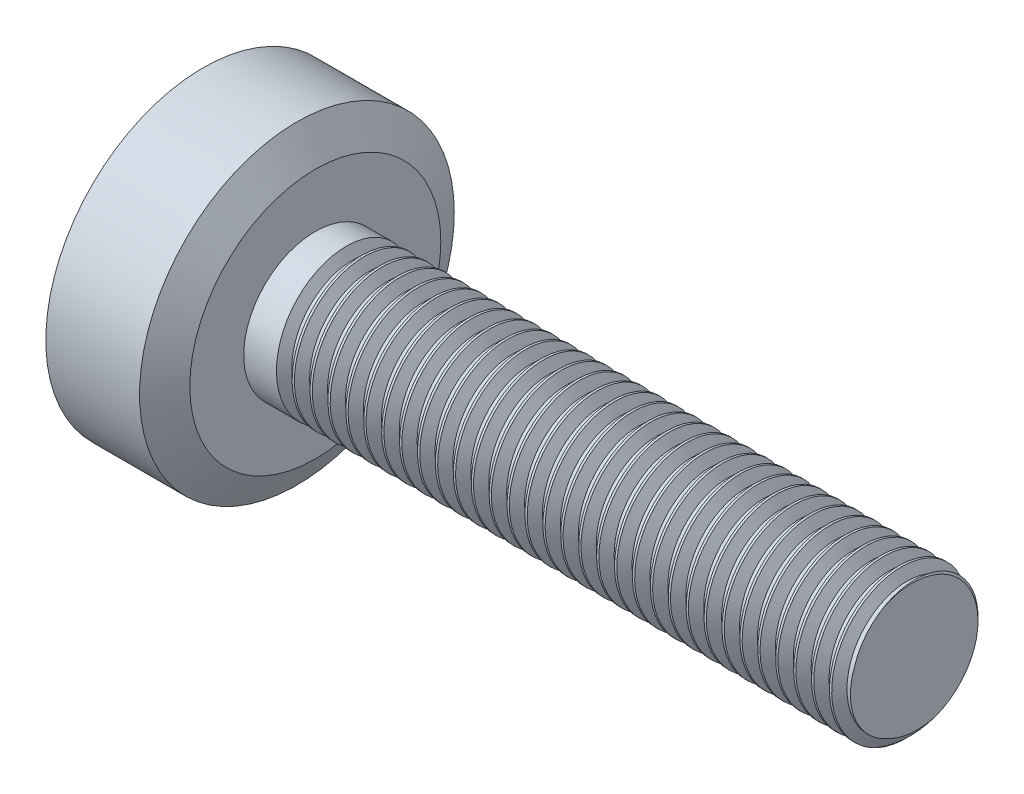
SolidWorks part; units mm, degrees
ref_plane "Front Plane" through (0, 0, 0) normal (0, 0, 1) x (1, 0, 0)
ref_plane "Top Plane" through (0, 0, 0) normal (0, 1, 0) x (1, 0, 0)
ref_plane "Right Plane" through (0, 0, 0) normal (1, 0, 0) x (0, 0, -1)
sketch "Sketch3" plane through (0, 0, 0) normal (0, 1, 0) x (1, 0, 0)
  line L0 (0, 0) -> (62, 0) construction
  line L1 (0, 0) -> (0, 9)
  line L2 (0, 9) -> (2.6092, 13.1776)
  line L3 (2.6092, 13.1776) -> (10.46, 13.1776)
  line L4 (10.46, 13.1776) -> (12, 10.5103)
  line L5 (12, 10.5103) -> (12, 6)
  line L6 (12, 6) -> (62, 6)
  line L7 (62, 6) -> (62, 0)
  line L8 (62, 0) -> (0, 0)
  dimension "D1" = 6
  dimension "D2" = 50
  dimension "D3" = 12
  dimension "D4" = 9
revolve "Revolve1" add sketch "Sketch3" angle 360 about L8
chamfer "Chamfer1" distance 0.5 angle 45 1 edges at (62, 0, -6)
sketch "Sketch4" plane through (0, 0, 0) normal (-1, 0, 0) x (0, 0, 1)
  line L1 (4.5, -2.5981) -> (4.5, 2.5981)
  line L2 (4.5, 2.5981) -> (0, 5.1962)
  line L3 (0, 5.1962) -> (-4.5, 2.5981)
  line L4 (-4.5, 2.5981) -> (-4.5, -2.5981)
  line L5 (-4.5, -2.5981) -> (0, -5.1962)
  line L6 (0, -5.1962) -> (4.5, -2.5981)
  circle A0 centre (0, 0) radius 4.5 construction
  dimension "D1" = 9
extrude "Cut-Extrude1" cut sketch "Sketch4" against normal blind 8
sketch "Sketch5" plane through (0, 0, 0) normal (0, 0, 1) x (1, 0, 0)
  line L0 (0, 0) -> (18.7784, 0) construction
  line L1 (0, 0) -> (0, 6)
  line L2 (0, 9) -> (0, -9) construction
  line L3 (0, 6) -> (3.4641, 0)
  line L4 (3.4641, 0) -> (0, 0)
  line L5 (7.7643, 0) -> (7.7643, 5.7407)
  line L6 (7.7643, 5.7407) -> (11.0788, 0)
  line L7 (11.0788, 0) -> (7.7643, 0)
  dimension "D1" = 30
  dimension "D2" = 30
revolve "Cut-Revolve1" cut sketch "Sketch5" angle 360 about L0
thread "Thread1" pitch 1.5 method cut profile "Thread Profile1" start angle 0, offset 2, length 0, pitch 1.5, diameter 12
ref_plane "Plane1" through (14, 0, -6) normal (0, -1, 0) x (0, 0, -1)
sketch "Thread Profile1" plane through (14, 0, -6) normal (0, -1, 0) x (0, 0, -1)
  line L0 (0, 0) -> (0, 1.5) construction
  line L11 (0, 0) -> (0, 1.3125)
  line L12 (0, 1.3125) -> (-0.8119, 0.8437)
  line L13 (-0.8119, 0.8437) -> (-0.8119, 0.4687)
  line L15 (-0.8119, 0.4687) -> (0, 0)
  line L17 (-0.8119, 0.6562) -> (0, 0.6562) construction
  point P2 (0, 0)
  dimension "Pitch" = 1.5
  dimension "Profile_Angle" = 60
  dimension "Profile_Land" = 0.375
  dimension "Profile_Height" = 0.8119
